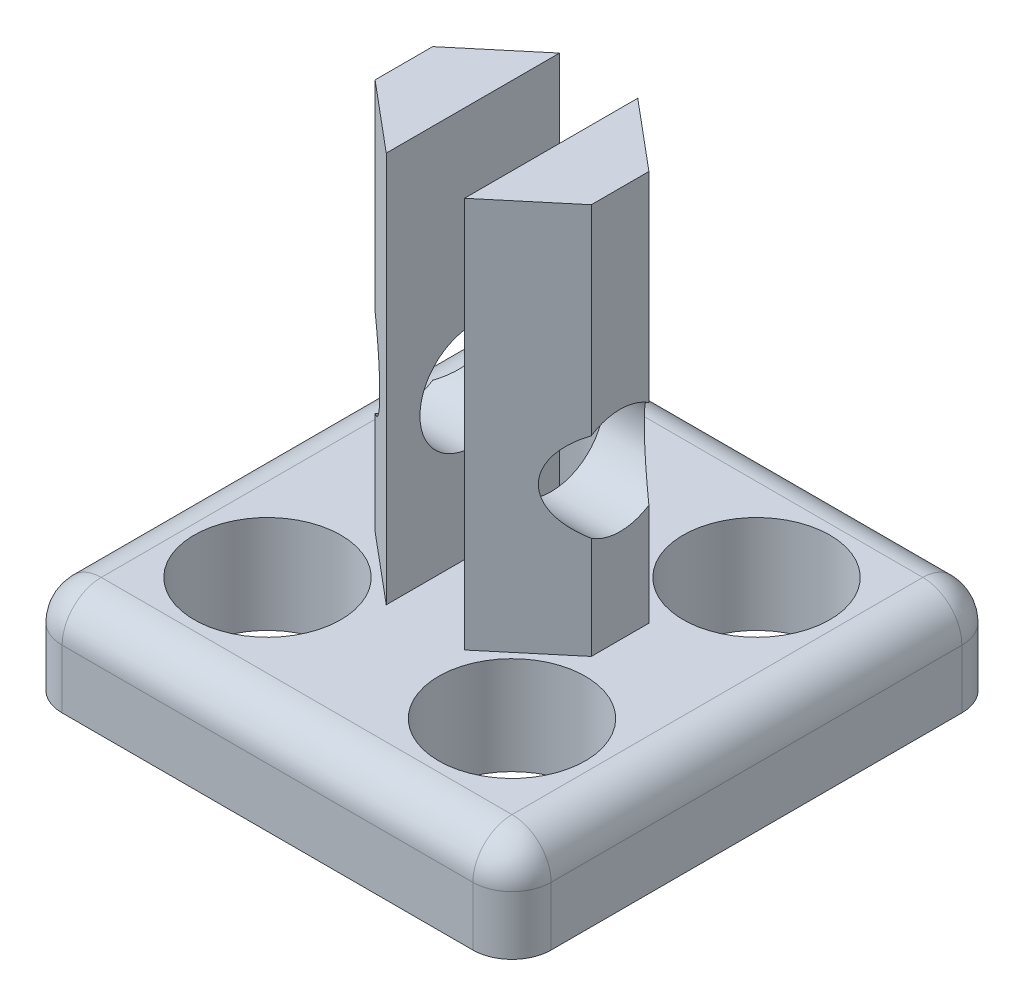
SolidWorks part; units mm, degrees
ref_plane "Front Plane" through (0, 0, 0) normal (0, 0, 1) x (1, 0, 0)
ref_plane "Top Plane" through (0, 0, 0) normal (0, 1, 0) x (1, 0, 0)
ref_plane "Right Plane" through (0, 0, 0) normal (1, 0, 0) x (0, 0, -1)
sketch "Sketch1" plane through (0, 0, 0) normal (0, 1, 0) x (1, 0, 0)
  line L0 (0, 12.208) -> (0, -19.1109) construction
  line L1 (-6.35, -6.35) -> (6.35, -6.35)
  line L2 (-6.35, -6.35) -> (-6.35, 6.35)
  line L3 (-6.35, 6.35) -> (6.35, 6.35)
  line L4 (6.35, -6.35) -> (6.35, 6.35)
  line L5 (-6.35, -6.35) -> (6.35, 6.35) construction
  line L6 (-6.35, 6.35) -> (6.35, -6.35) construction
  line L7 (-21.3979, 0) -> (34.337, 0) construction
  circle A0 centre (-3.175, 3.175) radius 1.905
  circle A1 centre (3.175, 3.175) radius 1.905
  circle A2 centre (3.175, -3.175) radius 1.905
  circle A3 centre (-3.175, -3.175) radius 1.905
  point P0 (0, 0)
  point P18 (0, 0)
  point P19 (0, 0)
  dimension "D3" = 3.81
  dimension "D1" = 12.7
  dimension "D2" = 12.7
  dimension "D4" = 3.175
extrude "Boss-Extrude1" add sketch "Sketch1" along normal blind 2.54
sketch "Sketch2" plane through (0, 2.54, 0) normal (0, 1, 0) x (1, 0, 0)
  line L0 (0, 0) -> (-7.7131, 0) construction
  line L5 (-1.016, 5.1275) -> (1.016, 5.1275)
  line L6 (2.8079, -0.748) -> (2.8079, 0.748)
  line L8 (-1.016, -5.1275) -> (1.016, -5.1275)
  line L9 (-1.016, -5.1275) -> (-1.016, 5.1275)
  line L11 (1.016, -5.1275) -> (1.016, 5.1275)
  line L12 (-1.016, -5.1275) -> (1.016, 5.1275) construction
  line L13 (-1.016, 5.1275) -> (1.016, -5.1275) construction
  line L14 (0, 0) -> (0, 7.6198) construction
  line L15 (-2.8079, 0.748) -> (-2.8079, -0.748)
  line L20 (-2.8079, 0.748) -> (-1.016, 2.2498)
  line L21 (-4.424, -0.748) -> (4.424, -0.748)
  line L22 (-4.424, -0.748) -> (-4.424, 0.748)
  line L23 (-4.424, 0.748) -> (4.424, 0.748)
  line L24 (4.424, -0.748) -> (4.424, 0.748)
  line L25 (-4.424, -0.748) -> (4.424, 0.748) construction
  line L26 (-4.424, 0.748) -> (4.424, -0.748) construction
  line L27 (2.8079, 0.748) -> (1.016, 2.2498)
  line L28 (2.8079, -0.748) -> (1.016, -2.2498)
  line L29 (-2.8079, -0.748) -> (-1.016, -2.2498)
  point P0 (0, 0)
  point P1 (0, 0)
  point P3 (0, 0)
  point P6 (-1.16, 2.2498)
  point P7 (0, 0)
  point P8 (0, 0)
  dimension "D1" = 2.032
  dimension "D2" = 0
extrude "Boss-Extrude2" add sketch "Sketch2" along normal blind 10.16 contours L20 L23 L9 | L23 L15 L21 L9 | L21 L29 L9 | L23 L27 L11 | L23 L11 L21 L6 | L28 L21 L11 region at (-1.6133, 2.54, -1.2486) region at (1.6133, 2.54, -1.2486) region at (-1.9119, 2.54, 0) region at (1.9119, 2.54, 0) region at (-1.6133, 2.54, 1.2486) region at (1.6133, 2.54, 1.2486)
sketch "Sketch3" plane through (2.8079, 0, 0) normal (1, 0, 0) x (0, 0, -1)
  line L0 (-0.748, 2.54) -> (0.748, 2.54) construction
  circle A0 centre (0, 6.35) radius 1.375
  dimension "D1" = 2.75
  dimension "D2" = 3.81
extrude "Cut-Extrude1" cut sketch "Sketch3" against normal through all
fillet "Fillet1" radius 1.016 8 edges at (6.35, 1.27, -6.35) (0, 2.54, -6.35) (-6.35, 1.27, -6.35) (-6.35, 1.27, 6.35) (-6.35, 2.54, 0) (6.35, 1.27, 6.35) (6.35, 2.54, 0) (0, 2.54, 6.35)
